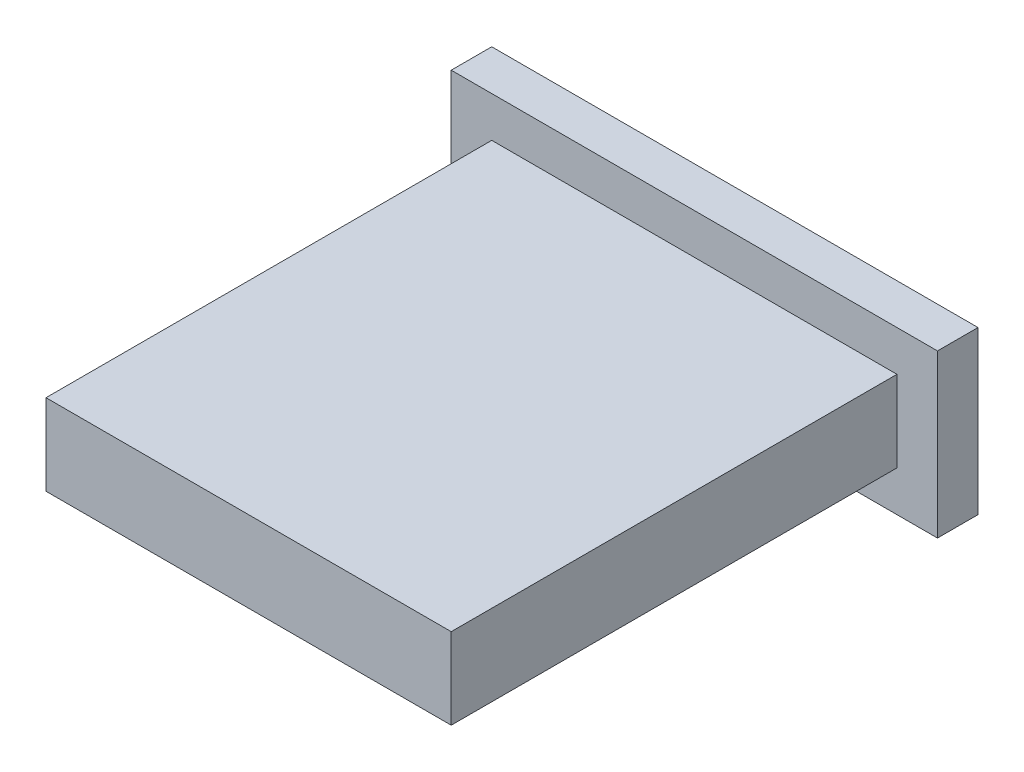
SolidWorks part; units mm, degrees
ref_plane "Piano frontale" through (0, 0, 0) normal (0, 0, 1) x (1, 0, 0)
ref_plane "Piano superiore" through (0, 0, 0) normal (0, 1, 0) x (1, 0, 0)
ref_plane "Piano destro" through (0, 0, 0) normal (1, 0, 0) x (0, 0, -1)
sketch "Schizzo1" plane through (0, 0, 0) normal (0, 0, 1) x (1, 0, 0)
  line L1 (-6, 2) -> (6, 2)
  line L2 (-6, 2) -> (-6, -2)
  line L3 (-6, -2) -> (6, -2)
  line L4 (6, 2) -> (6, -2)
  line L5 (-5, 1) -> (5, 1)
  line L6 (-5, 1) -> (-5, -1)
  line L7 (-5, -1) -> (5, -1)
  line L8 (5, 1) -> (5, -1)
  point P8 (0, 1)
  point P9 (5, 0)
  dimension "D1" = 10
  dimension "D2" = 2
  dimension "D3" = 12
  dimension "D4" = 1
  dimension "D5" = 4
  dimension "D6" = 1
extrude "Estrusione-Estrusione1" add sketch "Schizzo1" along normal blind 11 contours L5 L8 L7 L6
extrude "Estrusione-Estrusione2" add sketch "Schizzo1<4>" against normal blind 1 separate body
sketch "Schizzo1<4>" plane through (0, 0, 0) normal (0, 0, 1) x (1, 0, 0) same geometry as "Schizzo1"
